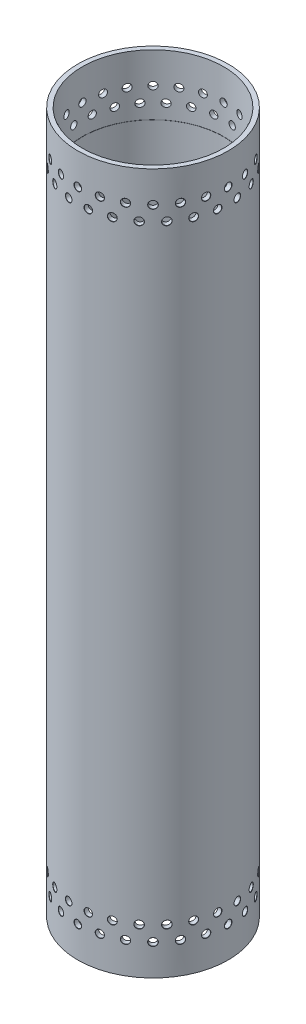
SolidWorks part; units mm, degrees
material "AW-6082-T6 (PA4)"
ref_plane "Płaszczyzna przednia" through (0, 0, 0) normal (0, 0, 1) x (1, 0, 0)
ref_plane "Płaszczyzna górna" through (0, 0, 0) normal (0, 1, 0) x (1, 0, 0)
ref_plane "Płaszczyzna prawa" through (0, 0, 0) normal (1, 0, 0) x (0, 0, -1)
sketch "Szkic1" plane through (0, 0, 0) normal (0, 1, 0) x (1, 0, 0)
  circle A0 centre (0, 0) radius 90
  circle A1 centre (0, 0) radius 81.5
  dimension "D1" = 8.5
  dimension "D2" = 180
  dimension "D3" = 163
extrude "Dodanie-wyciągnięcie1" add sketch "Szkic1" along normal blind 810
sketch "Szkic2" plane through (0, 810, 0) normal (0, 1, 0) x (1, 0, 0)
  circle A0 centre (0, 0) radius 87
  circle A1 centre (0, 0) radius 90 construction
  circle A2 centre (0, 0) radius 90
  dimension "D1" = 174
extrude "Wytnij-wyciągnięcie1" cut sketch "Szkic2" against normal through all
sketch "Szkic3" plane through (0, 810, 0) normal (0, 1, 0) x (1, 0, 0)
  circle A0 centre (0, 0) radius 81.7
  circle A1 centre (0, 0) radius 81.5 construction
  circle A2 centre (0, 0) radius 81.5
  dimension "D1" = 0.2
extrude "Wytnij-wyciągnięcie2" cut sketch "Szkic3" against normal blind 70
ref_plane "Płaszczyzna1" through (0, 0, 87) normal (0, 0, 1) x (1, 0, 0)
ref_plane "Płaszczyzna2" through (11.3558, 0, 86.2557) normal (0.1305, 0, 0.9914) x (0, 1, 0)
hole_wizard "Otwór Ø8.5 (8.5)1" positions "Szkic5" profile "Szkic6" hole size "Ø8.5" standard "DIN" end condition up to next
sketch "Szkic5" plane through (0, 0, 87) normal (0, 0, 1) x (1, 0, 0)
  line L0 (87, 810) -> (-87, 810) construction
  line L1 (87, 0) -> (87, 810) construction
  line L2 (-87, 810) -> (-87, 0) construction
  line L3 (87, 0) -> (87, 810)
  line L4 (-87, 810) -> (-87, 0)
  line L5 (0, 869.2816) -> (0, 760.9563) construction
  point P0 (0, 774)
  dimension "D1" = 36
sketch "Szkic6" plane through (0, 774, 87) normal (1, 0, 0) x (0, -1, 0)
  line L0 (0, 0) -> (0, 5.3)
  line L1 (0, 5.3) -> (4.25, 5.3)
  line L2 (4.25, 5.3) -> (4.25, 0.25)
  line L3 (4.25, 0.25) -> (4.5, 0)
  line L5 (4.5, 0) -> (0, 0)
  line L6 (-4.25, 0.25) -> (-4.5, 0) construction
  line L11 (0, -6.35) -> (0, 107.95) construction
  dimension "Średnica otworu na wylot" = 8.5
  dimension "Głębokość otworu na wylot" = 5.3
  dimension "Średnica zewnętrznego pogłębienia stożkowego" = 9
  dimension "Kąt zewnętrznego pogłębienia stożkowego" = 90
hole_wizard "Otwór Ø8.5 (8.5)2" positions "Szkic7" profile "Szkic8" hole size "Ø8.5" standard "BSI" end condition up to next
sketch "Szkic7" plane through (11.3558, 0, 86.2557) normal (0.1305, 0, 0.9914) x (0, 1, 0)
  line L0 (810, -87) -> (810, 87) construction
  line L1 (0, -87) -> (810, -87) construction
  line L2 (810, 87) -> (0, 87) construction
  line L3 (0, -87) -> (810, -87)
  line L4 (810, 87) -> (0, 87)
  line L5 (862.9512, 0) -> (744.0524, 0) construction
  ellipse E0 centre (774, 11.3231) end of major axis (778.25, 11.3231) minor radius 4.2136 construction
  point P0 (757, 0)
  dimension "D1" = 53
  dimension "D2" = 20.4258
sketch "Szkic8" plane through (11.3558, 757, 86.2557) normal (0, 1, 0) x (0.9914, 0, -0.1305)
  line L0 (0, 0) -> (0, 5.3)
  line L1 (0, 5.3) -> (4.25, 5.3)
  line L2 (4.25, 5.3) -> (4.25, 0.25)
  line L3 (4.25, 0.25) -> (4.5, 0)
  line L5 (4.5, 0) -> (0, 0)
  line L6 (-4.25, 0.25) -> (-4.5, 0) construction
  line L11 (0, -6.35) -> (0, 107.95) construction
  dimension "Średnica otworu na wylot" = 8.5
  dimension "Głębokość otworu na wylot" = 5.3
  dimension "Średnica zewnętrznego pogłębienia stożkowego" = 9
  dimension "Kąt zewnętrznego pogłębienia stożkowego" = 90
pattern_circular "Szyk kołowy1" count 24 over 360 about axis through (0, 0, 0) along (0, 1, 0) of "Otwór Ø8.5 (8.5)1", "Otwór Ø8.5 (8.5)2" reverse direction yes
ref_plane "Płaszczyzna3" through (0, 405, 0) normal (0, 1, 0) x (1, 0, 0)
mirror "Lustro1" about plane through (0, 405, 0) normal (0, 1, 0) of "Otwór Ø8.5 (8.5)2", "Otwór Ø8.5 (8.5)1", "Szyk kołowy1", "Wytnij-wyciągnięcie2"
